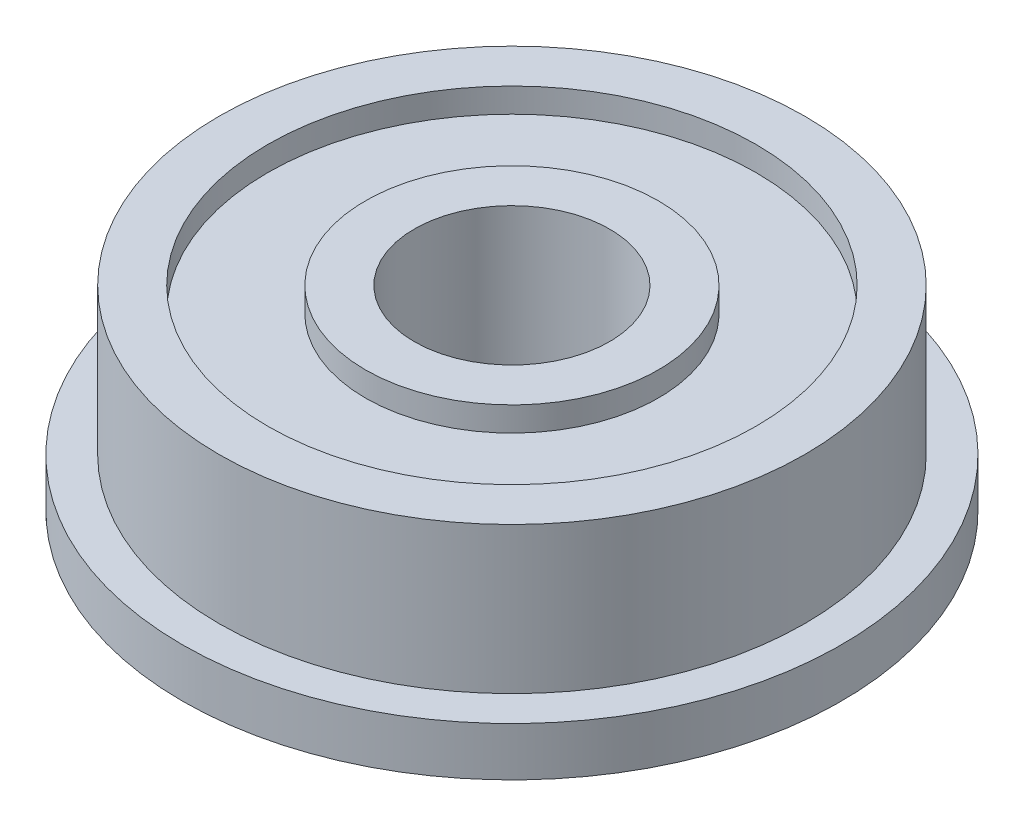
SolidWorks part; units mm, degrees
ref_plane "前基準面" through (0, 0, 0) normal (0, 0, 1) x (1, 0, 0)
ref_plane "上基準面" through (0, 0, 0) normal (0, 1, 0) x (1, 0, 0)
ref_plane "右基準面" through (0, 0, 0) normal (1, 0, 0) x (0, 0, -1)
sketch "草圖1" plane through (0, 0, 0) normal (0, 1, 0) x (1, 0, 0)
  circle A0 centre (0, 0) radius 6750
  circle A1 centre (0, 0) radius 6000
  circle A2 centre (0, 0) radius 2000
  dimension "D1" = 4000
  dimension "D2" = 12000
  dimension "D3" = 13500
extrude "填料-伸長1" add sketch "草圖1" along normal blind 4000 contours A1 A2 region at (-5830.2944, 0, 0)
extrude "填料-伸長2" add sketch "草圖1<3>" along normal blind 1000 contours A0 A1 region at (-6559.0812, 0, 0)
sketch "草圖1<3>" plane through (0, 0, 0) normal (0, 1, 0) x (1, 0, 0) same geometry as "草圖1"
sketch "草圖2" plane through (0, 4000, 0) normal (0, 1, 0) x (1, 0, 0)
  circle A0 centre (0, 0) radius 3000
  circle A1 centre (0, 0) radius 5000
  dimension "D1" = 6000
  dimension "D2" = 10000
extrude "除料-伸長1" cut sketch "草圖2" against normal blind 500
sketch "草圖3" plane through (0, 0, 0) normal (0, -1, 0) x (1, 0, 0)
  circle A0 centre (0, 0) radius 3000
  circle A1 centre (0, 0) radius 5000
